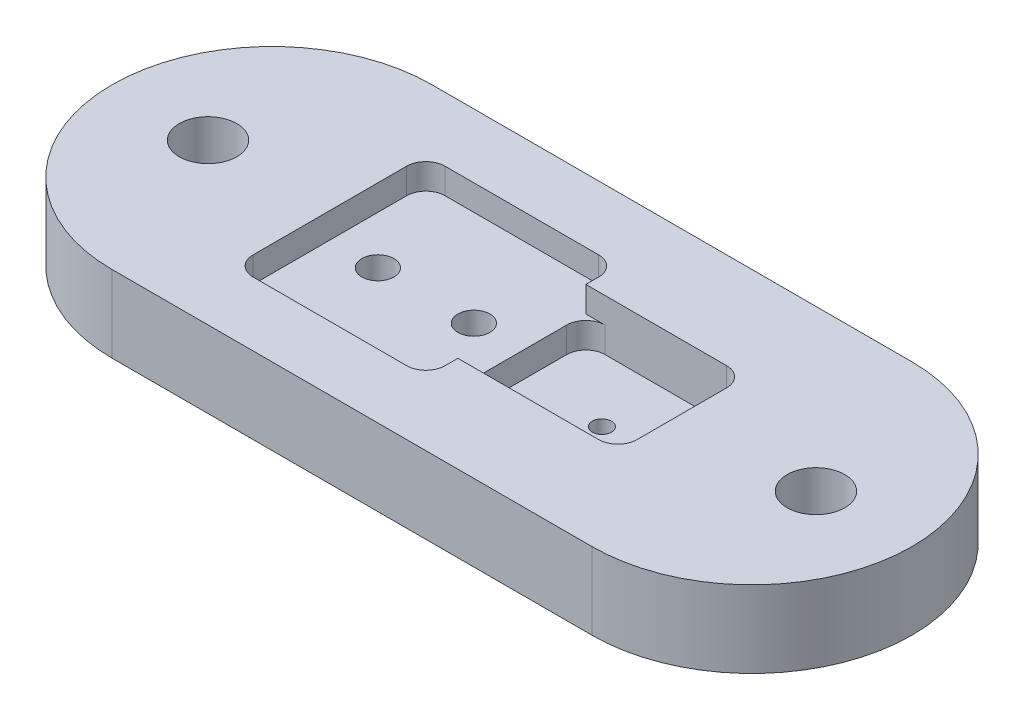
SolidWorks part; units mm, degrees
ref_plane "Front Plane" through (0, 0, 0) normal (0, 0, 1) x (1, 0, 0)
ref_plane "Top Plane" through (0, 0, 0) normal (0, 1, 0) x (1, 0, 0)
ref_plane "Right Plane" through (0, 0, 0) normal (1, 0, 0) x (0, 0, -1)
sketch "Sketch1" plane through (0, 0, 0) normal (0, 1, 0) x (1, 0, 0)
  line L1 (0, 0) -> (75, 0)
  line L2 (0, 0) -> (0, 50)
  line L3 (0, 50) -> (75, 50)
  line L4 (75, 0) -> (75, 50)
  arc A0 (75, 0) -> (75, 50) centre (75, 25) ccw
  arc A1 (0, 50) -> (0, 0) centre (0, 25) ccw
  dimension "D1" = 50
  dimension "D2" = 75
extrude "Boss-Extrude1" add sketch "Sketch1" along normal blind 12 contours L1 L4 L3 L2 | L4 A0 | L2 A1 region at (37.5, 0, -25) region at (-10.6103, 0, -25) region at (85.6103, 0, -25)
sketch "Sketch2" plane through (0, 12, 0) normal (0, 1, 0) x (1, 0, 0)
  line L0 (-25, 25) -> (100, 25) construction
  line L1 (37.5, 50) -> (37.5, 0) construction
  line L2 (0, 50) -> (75, 50) construction
  line L3 (0, 0) -> (75, 0) construction
  circle A0 centre (-10, 25) radius 4.5
  arc A1 (0, 50) -> (0, 0) centre (0, 25) ccw construction
  arc A2 (75, 0) -> (75, 50) centre (75, 25) ccw construction
  circle A3 centre (85, 25) radius 4.5
  dimension "D1" = 9
  dimension "D2" = 15
extrude "Cut-Extrude1" cut sketch "Sketch2" against normal through all
sketch "Sketch3" plane through (0, 12, 0) normal (0, 1, 0) x (1, 0, 0)
  line L0 (-25, 25) -> (100, 25) construction
  line L1 (9.0414, 40) -> (39.0414, 40)
  line L2 (9.0414, 40) -> (9.0414, 10)
  line L3 (9.0414, 10) -> (39.0414, 10)
  line L4 (39.0414, 40) -> (39.0414, 10)
  arc A0 (0, 50) -> (0, 0) centre (0, 25) ccw construction
  arc A1 (75, 0) -> (75, 50) centre (75, 25) ccw construction
  point P12 (9.0414, 25)
  dimension "D1" = 30
  dimension "D2" = 30
extrude "Cut-Extrude2" cut sketch "Sketch3" against normal blind 4
sketch "Sketch4" plane through (0, 12, 0) normal (0, 1, 0) x (1, 0, 0)
  line L0 (-25, 25) -> (100, 25) construction
  line L1 (39.0414, 10) -> (39.0414, 40) construction
  line L2 (39.0414, 35) -> (64.0414, 35)
  line L3 (39.0414, 35) -> (39.0414, 15)
  line L4 (39.0414, 15) -> (64.0414, 15)
  line L5 (64.0414, 35) -> (64.0414, 15)
  arc A0 (0, 50) -> (0, 0) centre (0, 25) ccw construction
  arc A1 (75, 0) -> (75, 50) centre (75, 25) ccw construction
  point P14 (64.0414, 25)
  dimension "D1" = 20
  dimension "D2" = 25
extrude "Cut-Extrude3" cut sketch "Sketch4" against normal blind 8 contours L3 L2 L5 L4
fillet "Fillet1" radius 3 8 edges at (39.0414, 6, -35) (39.0414, 6, -15) (64.0414, 8, -15) (64.0414, 8, -35) (39.0414, 10, -10) (9.0414, 10, -10) (9.0414, 10, -40) (39.0414, 10, -40)
sketch "Sketch5" plane through (0, 4, 0) normal (0, 1, 0) x (1, 0, 0)
  line L0 (51.5414, 35) -> (51.5414, 15) construction
  line L1 (42.0414, 35) -> (61.0414, 35) construction
  line L2 (42.0414, 15) -> (61.0414, 15) construction
  circle A0 centre (51.5414, 25) radius 1.5
  dimension "D1" = 3
extrude "Cut-Extrude4" cut sketch "Sketch5" against normal through all
sketch "Sketch6" plane through (0, 8, 0) normal (0, 1, 0) x (1, 0, 0)
  line L0 (9.0414, 25) -> (24.0414, 25) construction
  line L1 (9.0414, 37) -> (9.0414, 13) construction
  line L2 (24.0414, 25) -> (39.0414, 25) construction
  line L3 (39.0414, 32) -> (39.0414, 18) construction
  circle A0 centre (16.5414, 25) radius 2.5
  circle A1 centre (31.5414, 25) radius 2.5
  point P13 (16.5414, 25)
  point P16 (39.0414, 25)
  dimension "D1" = 5
extrude "Cut-Extrude5" cut sketch "Sketch6" against normal through all
